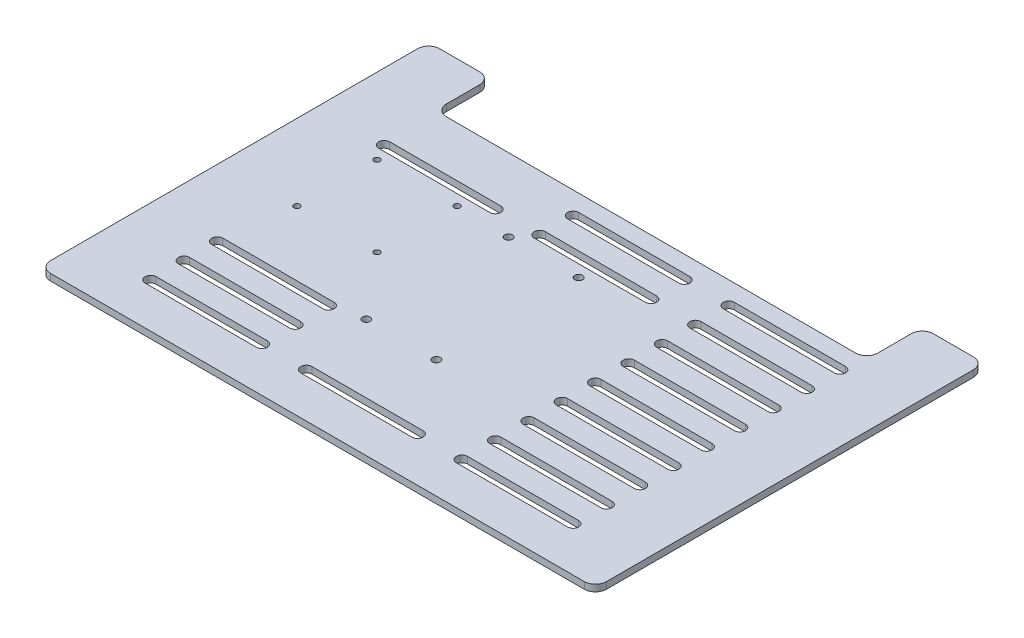
SolidWorks part; units mm, degrees
material "A-玻璃纤维"
ref_plane "前视基准面" through (0, 0, 0) normal (0, 0, 1) x (1, 0, 0)
ref_plane "上视基准面" through (0, 0, 0) normal (0, 1, 0) x (1, 0, 0)
ref_plane "右视基准面" through (0, 0, 0) normal (1, 0, 0) x (0, 0, -1)
other "Configuration Table"
sketch "草图1" plane through (0, 0, 0) normal (0, 1, 0) x (1, 0, 0)
  line L1 (-84.7342, 82.3595) -> (109.2658, 82.3595)
  line L2 (-112.7342, 55.552) -> (-112.7342, -67.6405)
  line L3 (-112.7342, -67.6405) -> (137.2658, -67.6405)
  line L4 (137.2658, 82.3595) -> (137.2658, -67.6405)
  line L5 (-112.7342, 55.552) -> (137.2658, -67.6405) construction
  line L6 (-112.7342, -67.6405) -> (137.2658, 82.3595) construction
  line L8 (-112.7342, 55.552) -> (-112.7342, 107.3595)
  line L9 (-112.7342, 107.3595) -> (-84.7342, 107.3595)
  line L10 (-84.7342, 82.3595) -> (-84.7342, 107.3595)
  line L12 (137.2658, 82.3595) -> (137.2658, 107.3595)
  line L13 (137.2658, 107.3595) -> (109.2658, 107.3595)
  line L14 (109.2658, 82.3595) -> (109.2658, 107.3595)
  point P0 (0, 0)
  dimension "D1" = 150
  dimension "D2" = 250
  dimension "D3" = 28
  dimension "D4" = 28
  dimension "D5" = 25
extrude "凸台-拉伸1" add sketch "草图1" along normal blind 3
fillet "圆角1" radius 5 8 edges at (137.2658, 1.5, 67.6405) (-112.7342, 1.5, 67.6405) (137.2658, 1.5, -107.3595) (109.2658, 1.5, -107.3595) (109.2658, 1.5, -82.3595) (-112.7342, 1.5, -107.3595) (-84.7342, 1.5, -107.3595) (-84.7342, 1.5, -82.3595)
sketch "草图4" plane through (0, 3, 0) normal (0, 1, 0) x (1, 0, 0)
  line L0 (57.2658, 72.3595) -> (107.2658, 72.3595) construction
  line L1 (57.2658, 74.8595) -> (107.2658, 74.8595)
  line L2 (57.2658, 69.8595) -> (107.2658, 69.8595)
  line L3 (57.2658, 57.3595) -> (107.2658, 57.3595) construction
  line L4 (104.2658, 82.3595) -> (-79.7342, 82.3595)
  line L5 (-112.7342, 102.3595) -> (-112.7342, -62.6405)
  line L6 (-107.7342, -67.6405) -> (132.2658, -67.6405)
  line L7 (137.2658, -62.6405) -> (137.2658, 102.3595)
  line L8 (104.2658, 82.3595) -> (-79.7342, 82.3595)
  line L9 (-112.7342, 102.3595) -> (-112.7342, -62.6405)
  line L11 (137.2658, -62.6405) -> (137.2658, 102.3595)
  line L12 (57.2658, 59.8595) -> (107.2658, 59.8595)
  line L13 (57.2658, 54.8595) -> (107.2658, 54.8595)
  line L14 (57.2658, 42.3595) -> (107.2658, 42.3595) construction
  line L15 (57.2658, 44.8595) -> (107.2658, 44.8595)
  line L16 (132.2658, 107.3595) -> (114.2658, 107.3595)
  line L17 (132.2658, 107.3595) -> (114.2658, 107.3595)
  line L18 (109.2658, 102.3595) -> (109.2658, 87.3595)
  line L19 (109.2658, 102.3595) -> (109.2658, 87.3595)
  line L20 (-84.7342, 87.3595) -> (-84.7342, 102.3595)
  line L21 (-84.7342, 87.3595) -> (-84.7342, 102.3595)
  line L22 (-89.7342, 107.3595) -> (-107.7342, 107.3595)
  line L23 (-89.7342, 107.3595) -> (-107.7342, 107.3595)
  line L24 (57.2658, 39.8595) -> (107.2658, 39.8595)
  line L25 (57.2658, 27.3595) -> (107.2658, 27.3595) construction
  line L26 (57.2658, 29.8595) -> (107.2658, 29.8595)
  line L27 (57.2658, 24.8595) -> (107.2658, 24.8595)
  line L28 (57.2658, 12.3595) -> (107.2658, 12.3595) construction
  line L29 (57.2658, 14.8595) -> (107.2658, 14.8595)
  line L30 (57.2658, 9.8595) -> (107.2658, 9.8595)
  line L31 (57.2658, -2.6405) -> (107.2658, -2.6405) construction
  line L32 (57.2658, -0.1405) -> (107.2658, -0.1405)
  line L33 (57.2658, -5.1405) -> (107.2658, -5.1405)
  line L34 (57.2658, -17.6405) -> (107.2658, -17.6405) construction
  line L35 (57.2658, -15.1405) -> (107.2658, -15.1405)
  line L36 (57.2658, -20.1405) -> (107.2658, -20.1405)
  line L37 (57.2658, -32.6405) -> (107.2658, -32.6405) construction
  line L38 (57.2658, -30.1405) -> (107.2658, -30.1405)
  line L39 (57.2658, -35.1405) -> (107.2658, -35.1405)
  line L40 (57.2658, -47.6405) -> (107.2658, -47.6405) construction
  line L41 (57.2658, -45.1405) -> (107.2658, -45.1405)
  line L42 (57.2658, -50.1405) -> (107.2658, -50.1405)
  line L52 (-12.7342, 72.3595) -> (37.2658, 72.3595) construction
  line L53 (-12.7342, 74.8595) -> (37.2658, 74.8595)
  line L54 (-12.7342, 69.8595) -> (37.2658, 69.8595)
  line L55 (-12.7342, 57.3595) -> (37.2658, 57.3595) construction
  line L56 (-12.7342, 59.8595) -> (37.2658, 59.8595)
  line L57 (-12.7342, 54.8595) -> (37.2658, 54.8595)
  line L58 (-82.7342, 72.3595) -> (-32.7342, 72.3595) construction
  line L59 (-82.7342, 74.8595) -> (-32.7342, 74.8595)
  line L60 (-82.7342, 69.8595) -> (-32.7342, 69.8595)
  line L61 (-82.7342, 57.3595) -> (-32.7342, 57.3595) construction
  line L62 (-82.7342, 59.8595) -> (-32.7342, 59.8595)
  line L63 (-82.7342, 54.8595) -> (-32.7342, 54.8595)
  line L64 (-12.7342, -47.6405) -> (37.2658, -47.6405) construction
  line L65 (-12.7342, -45.1405) -> (37.2658, -45.1405)
  line L66 (-12.7342, -50.1405) -> (37.2658, -50.1405)
  line L76 (-82.7342, -47.6405) -> (-32.7342, -47.6405) construction
  line L77 (-82.7342, -45.1405) -> (-32.7342, -45.1405)
  line L78 (-82.7342, -50.1405) -> (-32.7342, -50.1405)
  line L88 (-82.7342, -32.6405) -> (-32.7342, -32.6405) construction
  line L89 (-82.7342, -30.1405) -> (-32.7342, -30.1405)
  line L90 (-82.7342, -35.1405) -> (-32.7342, -35.1405)
  line L91 (-82.7342, -17.6405) -> (-32.7342, -17.6405) construction
  line L92 (-82.7342, -15.1405) -> (-32.7342, -15.1405)
  line L93 (-82.7342, -20.1405) -> (-32.7342, -20.1405)
  line L149 (57.2658, -77.6405) -> (107.2658, -77.6405) construction
  line L150 (57.2658, -75.1405) -> (107.2658, -75.1405)
  line L151 (57.2658, -80.1405) -> (107.2658, -80.1405)
  line L152 (57.2658, -92.6405) -> (107.2658, -92.6405) construction
  line L153 (57.2658, -90.1405) -> (107.2658, -90.1405)
  line L154 (57.2658, -95.1405) -> (107.2658, -95.1405)
  line L155 (57.2658, -62.6405) -> (107.2658, -62.6405) construction
  line L156 (57.2658, -60.1405) -> (107.2658, -60.1405)
  line L157 (57.2658, -65.1405) -> (107.2658, -65.1405)
  line L158 (57.2658, -77.6405) -> (107.2658, -77.6405) construction
  line L159 (57.2658, -75.1405) -> (107.2658, -75.1405)
  line L160 (57.2658, -80.1405) -> (107.2658, -80.1405)
  line L161 (57.2658, -92.6405) -> (107.2658, -92.6405) construction
  line L162 (57.2658, -90.1405) -> (107.2658, -90.1405)
  line L163 (57.2658, -95.1405) -> (107.2658, -95.1405)
  line L164 (57.2658, -62.6405) -> (107.2658, -62.6405) construction
  line L165 (57.2658, -60.1405) -> (107.2658, -60.1405)
  line L166 (57.2658, -65.1405) -> (107.2658, -65.1405)
  circle A0 centre (-18.8913, -14.5) radius 1.75 construction
  circle A1 centre (12.6087, -14.5) radius 1.75 construction
  circle A2 centre (-42.5828, 49.995) radius 1.35 construction
  circle A3 centre (-18.8913, 49.5) radius 1.75 construction
  arc A4 (57.2658, 74.8595) -> (57.2658, 69.8595) centre (57.2658, 72.3595) ccw
  arc A5 (-112.7342, -62.6405) -> (-107.7342, -67.6405) centre (-107.7342, -62.6405) ccw
  arc A6 (132.2658, -67.6405) -> (137.2658, -62.6405) centre (132.2658, -62.6405) ccw
  arc A7 (107.2658, 69.8595) -> (107.2658, 74.8595) centre (107.2658, 72.3595) ccw
  arc A9 (-112.7342, -62.6405) -> (-107.7342, -67.6405) centre (-107.7342, -62.6405) ccw
  arc A10 (132.2658, -67.6405) -> (137.2658, -62.6405) centre (132.2658, -62.6405) ccw
  circle A12 centre (12.6087, 49.5) radius 1.75 construction
  circle A13 centre (-18.8913, -14.5) radius 1.75
  circle A14 centre (12.6087, -14.5) radius 1.75
  circle A15 centre (-42.5828, 49.995) radius 1.35
  circle A16 centre (-18.8913, 49.5) radius 1.75
  circle A17 centre (12.6087, 49.5) radius 1.75
  circle A18 centre (-42.5828, 13.995) radius 1.35 construction
  circle A19 centre (-78.5828, 13.995) radius 1.35 construction
  circle A20 centre (-78.5828, 49.995) radius 1.35 construction
  circle A21 centre (-42.5828, 13.995) radius 1.35
  circle A22 centre (-78.5828, 13.995) radius 1.35
  circle A23 centre (-78.5828, 49.995) radius 1.35
  arc A24 (57.2658, 59.8595) -> (57.2658, 54.8595) centre (57.2658, 57.3595) ccw
  arc A25 (107.2658, 54.8595) -> (107.2658, 59.8595) centre (107.2658, 57.3595) ccw
  arc A26 (57.2658, 44.8595) -> (57.2658, 39.8595) centre (57.2658, 42.3595) ccw
  arc A27 (107.2658, 39.8595) -> (107.2658, 44.8595) centre (107.2658, 42.3595) ccw
  arc A28 (57.2658, 29.8595) -> (57.2658, 24.8595) centre (57.2658, 27.3595) ccw
  arc A29 (107.2658, 24.8595) -> (107.2658, 29.8595) centre (107.2658, 27.3595) ccw
  arc A30 (57.2658, 14.8595) -> (57.2658, 9.8595) centre (57.2658, 12.3595) ccw
  arc A32 (107.2658, 9.8595) -> (107.2658, 14.8595) centre (107.2658, 12.3595) ccw
  arc A34 (57.2658, -0.1405) -> (57.2658, -5.1405) centre (57.2658, -2.6405) ccw
  arc A36 (107.2658, -5.1405) -> (107.2658, -0.1405) centre (107.2658, -2.6405) ccw
  arc A38 (57.2658, -15.1405) -> (57.2658, -20.1405) centre (57.2658, -17.6405) ccw
  arc A40 (107.2658, -20.1405) -> (107.2658, -15.1405) centre (107.2658, -17.6405) ccw
  arc A42 (57.2658, -30.1405) -> (57.2658, -35.1405) centre (57.2658, -32.6405) ccw
  arc A43 (107.2658, -35.1405) -> (107.2658, -30.1405) centre (107.2658, -32.6405) ccw
  arc A44 (57.2658, -45.1405) -> (57.2658, -50.1405) centre (57.2658, -47.6405) ccw
  arc A45 (107.2658, -50.1405) -> (107.2658, -45.1405) centre (107.2658, -47.6405) ccw
  arc A52 (-12.7342, 74.8595) -> (-12.7342, 69.8595) centre (-12.7342, 72.3595) ccw
  arc A53 (37.2658, 69.8595) -> (37.2658, 74.8595) centre (37.2658, 72.3595) ccw
  arc A54 (-12.7342, 59.8595) -> (-12.7342, 54.8595) centre (-12.7342, 57.3595) ccw
  arc A55 (37.2658, 54.8595) -> (37.2658, 59.8595) centre (37.2658, 57.3595) ccw
  arc A56 (-82.7342, 74.8595) -> (-82.7342, 69.8595) centre (-82.7342, 72.3595) ccw
  arc A57 (-32.7342, 69.8595) -> (-32.7342, 74.8595) centre (-32.7342, 72.3595) ccw
  arc A58 (-82.7342, 59.8595) -> (-82.7342, 54.8595) centre (-82.7342, 57.3595) ccw
  arc A59 (-32.7342, 54.8595) -> (-32.7342, 59.8595) centre (-32.7342, 57.3595) ccw
  arc A60 (-12.7342, -45.1405) -> (-12.7342, -50.1405) centre (-12.7342, -47.6405) ccw
  arc A61 (37.2658, -50.1405) -> (37.2658, -45.1405) centre (37.2658, -47.6405) ccw
  arc A68 (-82.7342, -45.1405) -> (-82.7342, -50.1405) centre (-82.7342, -47.6405) ccw
  arc A69 (-32.7342, -50.1405) -> (-32.7342, -45.1405) centre (-32.7342, -47.6405) ccw
  arc A76 (-82.7342, -30.1405) -> (-82.7342, -35.1405) centre (-82.7342, -32.6405) ccw
  arc A77 (-32.7342, -35.1405) -> (-32.7342, -30.1405) centre (-32.7342, -32.6405) ccw
  arc A78 (-82.7342, -15.1405) -> (-82.7342, -20.1405) centre (-82.7342, -17.6405) ccw
  arc A79 (-32.7342, -20.1405) -> (-32.7342, -15.1405) centre (-32.7342, -17.6405) ccw
  arc A88 (137.2658, 102.3595) -> (132.2658, 107.3595) centre (132.2658, 102.3595) ccw
  arc A89 (137.2658, 102.3595) -> (132.2658, 107.3595) centre (132.2658, 102.3595) ccw
  arc A90 (114.2658, 107.3595) -> (109.2658, 102.3595) centre (114.2658, 102.3595) ccw
  arc A91 (114.2658, 107.3595) -> (109.2658, 102.3595) centre (114.2658, 102.3595) ccw
  arc A92 (104.2658, 82.3595) -> (109.2658, 87.3595) centre (104.2658, 87.3595) ccw
  arc A93 (104.2658, 82.3595) -> (109.2658, 87.3595) centre (104.2658, 87.3595) ccw
  arc A94 (-84.7342, 87.3595) -> (-79.7342, 82.3595) centre (-79.7342, 87.3595) ccw
  arc A95 (-84.7342, 87.3595) -> (-79.7342, 82.3595) centre (-79.7342, 87.3595) ccw
  arc A96 (-84.7342, 102.3595) -> (-89.7342, 107.3595) centre (-89.7342, 102.3595) ccw
  arc A97 (-84.7342, 102.3595) -> (-89.7342, 107.3595) centre (-89.7342, 102.3595) ccw
  arc A98 (-107.7342, 107.3595) -> (-112.7342, 102.3595) centre (-107.7342, 102.3595) ccw
  arc A99 (-107.7342, 107.3595) -> (-112.7342, 102.3595) centre (-107.7342, 102.3595) ccw
  arc A140 (57.2658, -75.1405) -> (57.2658, -80.1405) centre (57.2658, -77.6405) ccw
  arc A141 (107.2658, -80.1405) -> (107.2658, -75.1405) centre (107.2658, -77.6405) ccw
  arc A142 (57.2658, -90.1405) -> (57.2658, -95.1405) centre (57.2658, -92.6405) ccw
  arc A143 (107.2658, -95.1405) -> (107.2658, -90.1405) centre (107.2658, -92.6405) ccw
  arc A144 (57.2658, -60.1405) -> (57.2658, -65.1405) centre (57.2658, -62.6405) ccw
  arc A145 (107.2658, -65.1405) -> (107.2658, -60.1405) centre (107.2658, -62.6405) ccw
  point P38 (82.2658, 72.3595)
  point P47 (82.2658, 57.3595)
  point P54 (82.2658, 42.3595)
  point P61 (82.2658, 27.3595)
  point P68 (82.2658, 12.3595)
  point P75 (82.2658, -2.6405)
  point P82 (82.2658, -17.6405)
  point P89 (82.2658, -32.6405)
  point P96 (82.2658, -47.6405)
  point P103 (82.2658, -82.6405)
  point P110 (82.2658, -97.6405)
  point P124 (12.2658, 72.3595)
  point P131 (12.2658, 57.3595)
  point P138 (-57.7342, 72.3595)
  point P145 (-57.7342, 57.3595)
  point P152 (12.2658, -47.6405)
  point P159 (12.2658, -82.6405)
  point P166 (12.2658, -97.6405)
  point P173 (82.2658, -67.6405)
  point P180 (-57.7342, -47.6405)
  point P187 (-57.7342, -82.6405)
  point P194 (-57.7342, -97.6405)
  point P201 (12.2658, -67.6405)
  point P208 (-57.7342, -32.6405)
  point P215 (-57.7342, -17.6405)
  point P220 (-57.7342, -67.6405)
  point P272 (82.2658, -82.6405)
  point P279 (82.2658, -97.6405)
  point P286 (82.2658, -67.6405)
  point P293 (82.2658, -82.6405)
  point P300 (82.2658, -97.6405)
  point P307 (82.2658, -67.6405)
  point P314 (82.2658, -82.6405)
  point P321 (82.2658, -97.6405)
  point P328 (82.2658, -67.6405)
  point P335 (82.2658, -77.6405)
  point P342 (82.2658, -92.6405)
  point P349 (82.2658, -62.6405)
  point P356 (82.2658, -77.6405)
  point P363 (82.2658, -92.6405)
  point P370 (82.2658, -62.6405)
  point P377 (82.2658, -77.6405)
  point P384 (82.2658, -92.6405)
  point P391 (82.2658, -62.6405)
  dimension "D4" = 2.5
  dimension "D2" = 30
  dimension "D3" = 50
  dimension "D5" = 10
  dimension "D1" = 0
  dimension "D6" = 12
  dimension "D7" = 3
  dimension "D8" = 3
  dimension "D9" = 3
extrude "切除-拉伸2" cut sketch "草图4" against normal blind 10 contours A17 | A13 | A15 | A22 | A21 | A14 | A16 | A23 region at (-18.8913, 3, 14.5) region at (-42.5828, 3, -49.995) region at (12.6087, 3, -49.5) region at (-42.5828, 3, -13.995) region at (-78.5828, 3, -13.995)
extrude "切除-拉伸3" cut sketch "草图4<3>" against normal blind 10 contours L63 A59 L62 A58 | L54 A53 L53 A52 | L57 A55 L56 A54 | L93 A79 L92 A78 | L90 A77 L89 A76 | L78 A69 L77 A68 | L66 A61 L65 A60 | L42 A45 L41 A44 | L39 A43 L38 A42 | L36 A40 L35 A38 | L33 A36 L32 A34 | L30 A32 L29 A30 | L27 A29 L26 A28 | L24 A27 L15 A26 | L13 A25 L12 A24 | L2 A7 L1 A4
sketch "草图4<3>" plane through (0, 3, 0) normal (0, 1, 0) x (1, 0, 0) same geometry as "草图4"
